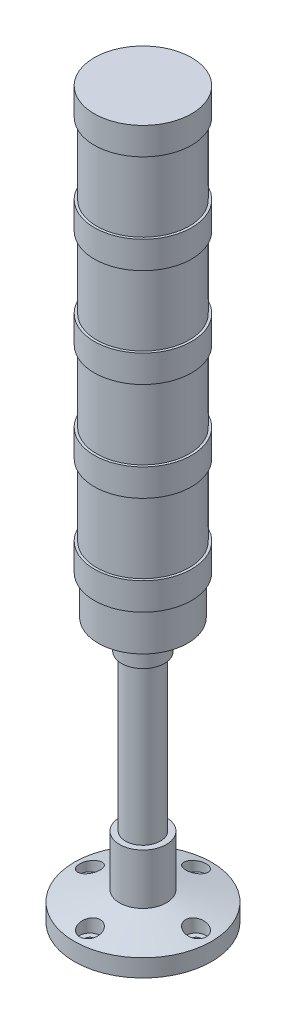
SolidWorks part; units mm, degrees
ref_plane "Płaszczyzna przednia" through (0, 0, 0) normal (0, 0, 1) x (1, 0, 0)
ref_plane "Płaszczyzna górna" through (0, 0, 0) normal (0, 1, 0) x (1, 0, 0)
ref_plane "Płaszczyzna prawa" through (0, 0, 0) normal (1, 0, 0) x (0, 0, -1)
sketch "Sketch1" plane through (0, 0, 0) normal (0, 1, 0) x (1, 0, 0)
  circle A0 centre (0, 0) radius 35.25
  dimension "D1" = 70.5
extrude "Boss-Extrude1" add sketch "Sketch1" along normal blind 9
sketch "Sketch2" plane through (0, 0, 0) normal (0, 0, 1) x (1, 0, 0)
  line L0 (0, 9) -> (0, 14.5)
  line L1 (0, 14.5) -> (12, 14.5)
  line L2 (12, 14.5) -> (35.25, 9)
  line L3 (35.25, 9) -> (0, 9)
  line L4 (35.25, 9) -> (-35.25, 9) construction
  dimension "D2" = 12
revolve "Revolve1" add sketch "Sketch2" angle 360 about L0
sketch "Sketch3" plane through (0, 14.5, 0) normal (0, 1, 0) x (1, 0, 0)
  circle A1 centre (0, 0) radius 12
  circle A2 centre (0, 0) radius 12
  dimension "D1" = 0
extrude "Boss-Extrude2" add sketch "Sketch3" along normal blind 26
sketch "Sketch4" plane through (0, 40.5, 0) normal (0, 1, 0) x (1, 0, 0)
  circle A0 centre (0, 0) radius 9
  dimension "D1" = 18
extrude "Boss-Extrude3" add sketch "Sketch4" along normal blind 80
sketch "Sketch5" plane through (0, 120.5, 0) normal (0, 1, 0) x (1, 0, 0)
  circle A0 centre (0, 0) radius 11
  dimension "D1" = 22
extrude "Boss-Extrude4" add sketch "Sketch5" along normal blind 10
sketch "Sketch6" plane through (0, 0, 0) normal (0, 0, 1) x (1, 0, 0)
  line L0 (0, 130.5) -> (0, 135.5)
  line L1 (11, 130.5) -> (-11, 130.5) construction
  line L2 (0, 135.5) -> (23, 135.5)
  line L3 (23, 135.5) -> (11, 130.5)
  line L4 (11, 130.5) -> (0, 130.5)
  dimension "D1" = 23
  dimension "D2" = 5
revolve "Revolve2" add sketch "Sketch6" angle 360 about L0
sketch "Sketch7" plane through (0, 135.5, 0) normal (0, 1, 0) x (1, 0, 0)
  circle A1 centre (0, 0) radius 23
  circle A2 centre (0, 0) radius 23
  dimension "D1" = 0
extrude "Boss-Extrude5" add sketch "Sketch7" along normal blind 20
sketch "Sketch8" plane through (0, 0, 0) normal (0, 0, 1) x (1, 0, 0)
  line L0 (0, 155.5) -> (25, 155.5)
  line L1 (23, 155.5) -> (-23, 155.5) construction
  line L2 (25, 155.5) -> (25, 169.5)
  line L3 (25, 169.5) -> (23.75, 169.5)
  line L4 (-25, 169.5) -> (-25, 155.5)
  line L5 (-25, 155.5) -> (0, 155.5)
  line L6 (0, 155.5) -> (0, 211.5328) construction
  line L8 (23.75, 169.5) -> (23.75, 206.1402)
  line L10 (-23.75, 206.1402) -> (-23.75, 169.5)
  line L12 (-25, 206.1402) -> (-23.75, 206.1402)
  line L13 (23.75, 206.1402) -> (25, 206.1402)
  line L14 (25, 206.1402) -> (25, 220.1402)
  line L15 (25, 220.1402) -> (23.75, 220.1402)
  line L16 (-25, 220.1402) -> (-25, 206.1402)
  line L19 (23.75, 220.1402) -> (23.75, 256.7803)
  line L21 (-23.75, 256.7803) -> (-23.75, 220.1402)
  line L22 (-25, 256.7803) -> (-23.75, 256.7803)
  line L23 (23.75, 256.7803) -> (25, 256.7803)
  line L24 (25, 256.7803) -> (25, 270.7803)
  line L25 (25, 270.7803) -> (23.75, 270.7803)
  line L26 (-25, 270.7803) -> (-25, 256.7803)
  line L29 (23.75, 270.7803) -> (23.75, 307.4205)
  line L31 (-23.75, 307.4205) -> (-23.75, 270.7803)
  line L32 (-25, 307.4205) -> (-23.75, 307.4205)
  line L33 (23.75, 307.4205) -> (25, 307.4205)
  line L34 (25, 307.4205) -> (25, 321.4205)
  line L35 (25, 321.4205) -> (23.75, 321.4205)
  line L36 (-25, 321.4205) -> (-25, 307.4205)
  line L39 (23.75, 321.4205) -> (23.75, 358.0607)
  line L41 (-23.75, 358.0607) -> (-23.75, 321.4205)
  line L42 (-25, 358.0607) -> (-23.75, 358.0607)
  line L43 (23.75, 358.0607) -> (25, 358.0607)
  line L44 (25, 358.0607) -> (25, 372.0607)
  line L45 (25, 372.0607) -> (-25, 372.0607)
  line L46 (-25, 372.0607) -> (-25, 358.0607)
  line L47 (-23.75, 169.5) -> (-25, 169.5)
  line L48 (0, 155.5) -> (0, 372.0607)
  line L49 (-23.75, 321.4205) -> (-25, 321.4205)
  line L51 (-23.75, 270.7803) -> (-25, 270.7803)
  line L53 (-23.75, 220.1402) -> (-25, 220.1402)
  dimension "D1" = 25
  dimension "D2" = 14
  dimension "D3" = 47.5
  dimension "D4" = 4
  dimension "D5" = 2
revolve "Revolve6" add sketch "Sketch8" angle 360 about L6 region at (-12.0841, 263.7803, 0)
sketch "Sketch9" plane through (0, 0, 0) normal (0, -1, 0) x (1, 0, 0)
  circle A0 centre (0, 27.25) radius 2.65
  circle A1 centre (27.25, 0) radius 2.65
  circle A2 centre (0, -27.25) radius 2.65
  circle A3 centre (-27.25, 0) radius 2.65
  point P12 (0, 0)
  dimension "D1" = 27.25
  dimension "D2" = 4
  dimension "D3" = 5.3
extrude "Cut-Extrude1" cut sketch "Sketch9" against normal blind 20
sketch "Sketch11" plane through (0, 0, 0) normal (0, 1, 0) x (1, 0, 0)
  circle A0 centre (0, 27.25) radius 5.25
  circle A1 centre (0, 27.25) radius 2.65 construction
  circle A2 centre (27.25, 0) radius 5.25
  circle A3 centre (0, -27.25) radius 5.25
  circle A4 centre (-27.25, 0) radius 5.25
  point P12 (0, 0)
  dimension "D1" = 10.5
  dimension "D2" = 4
extrude "Cut-Extrude2" cut sketch "Sketch11" against normal blind 40 from offset 45
